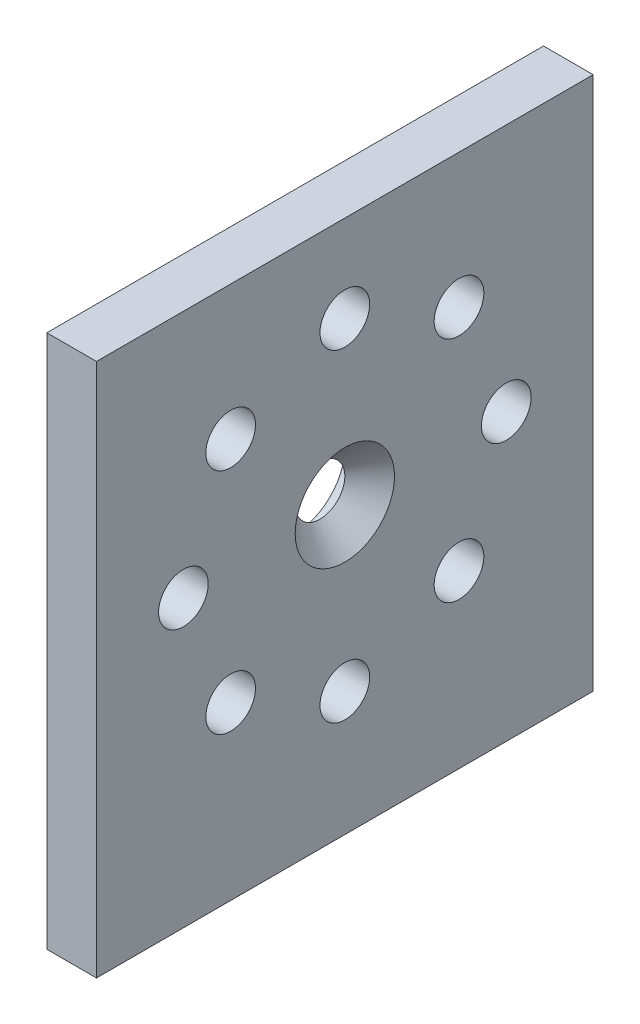
SolidWorks part; units mm, degrees
ref_plane "Plan de face" through (0, 0, 0) normal (0, 0, 1) x (1, 0, 0)
ref_plane "Plan de dessus" through (0, 0, 0) normal (0, 1, 0) x (1, 0, 0)
ref_plane "Plan de droite" through (0, 0, 0) normal (1, 0, 0) x (0, 0, -1)
sketch "Esquisse1" plane through (0, 0, 0) normal (0, 0, 1) x (1, 0, 0)
  line L0 (0, 0) -> (0, 43)
  line L1 (4, 0) -> (4, 43)
  line L2 (0, 0) -> (4, 0)
  line L3 (4, 43) -> (0, 43)
  dimension "D1" = 4
extrude "Extrusion1" add sketch "Esquisse1" along normal blind 40
sketch "Esquisse2" plane through (0, 0, 0) normal (-1, 0, 0) x (0, 0, 1)
  line L0 (20, 43) -> (20, 0) construction
  line L1 (40, 43) -> (0, 43) construction
  line L2 (40, 0) -> (0, 0) construction
  circle A0 centre (29.1924, 32.1924) radius 2
  circle A1 centre (20, 23) radius 2
  circle A2 centre (20, 36) radius 2
  circle A3 centre (33, 23) radius 2
  circle A4 centre (29.1924, 13.8076) radius 2
  circle A5 centre (20, 10) radius 2
  circle A6 centre (10.8076, 13.8076) radius 2
  circle A7 centre (7, 23) radius 2
  circle A8 centre (10.8076, 32.1924) radius 2
  dimension "D1" = 23
  dimension "D2" = 13
extrude "Extrusion2" cut sketch "Esquisse2" against normal through all
sketch "Esquisse3" plane through (0, 0, 0) normal (-1, 0, 0) x (0, 0, 1)
  circle A0 centre (20, 23) radius 4
extrude "Extrusion3" cut sketch "Esquisse3" against normal blind 2
chamfer "Chanfrein1" distance 2 angle 45 1 edges at (4, 23, 22)
